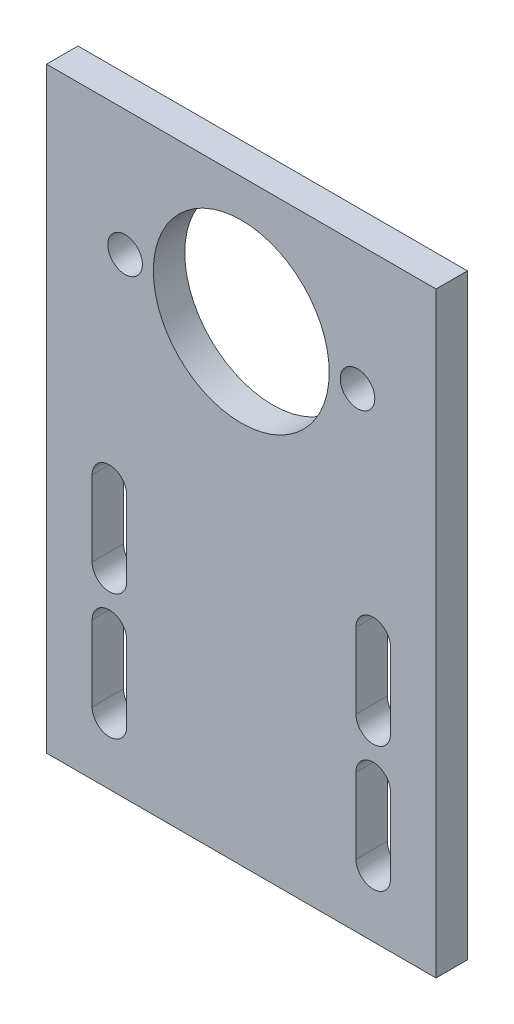
SolidWorks part; units mm, degrees
ref_plane "Front Plane" through (0, 0, 0) normal (0, 0, 1) x (1, 0, 0)
ref_plane "Top Plane" through (0, 0, 0) normal (0, 1, 0) x (1, 0, 0)
ref_plane "Right Plane" through (0, 0, 0) normal (1, 0, 0) x (0, 0, -1)
sketch "Sketch1" plane through (0, 0, 0) normal (0, 0, 1) x (1, 0, 0)
  line L0 (-4, 0) -> (-4, 100) construction
  line L1 (-35, -15) -> (27, -15) construction
  line L2 (-35, -15) -> (-35, 100)
  line L3 (-35, 100) -> (27, 100)
  line L4 (27, -15) -> (27, 100)
  line L5 (-35, -15) -> (27, 100) construction
  line L6 (-35, 100) -> (27, -15) construction
  line L7 (-22.5, 40) -> (14.5, 40) construction
  line L8 (-4, 0) -> (-4, -15) construction
  line L9 (-25, -5) -> (17, -5) construction
  line L10 (-35, -15) -> (-35, -35)
  line L11 (-25, -5) -> (-25, 7) construction
  line L12 (-35, -35) -> (27, -35)
  line L13 (27, -35) -> (27, -15)
  line L14 (-27.75, -5) -> (-27.75, 7)
  line L15 (-22.25, -5) -> (-22.25, 7)
  line L16 (17, -5) -> (17, 7) construction
  line L17 (19.75, -5) -> (19.75, 7)
  line L18 (14.25, -5) -> (14.25, 7)
  line L19 (-25, -25) -> (-25, -13) construction
  line L20 (-27.75, -25) -> (-27.75, -13)
  line L21 (-22.25, -25) -> (-22.25, -13)
  line L22 (17, -25) -> (17, -13) construction
  line L23 (19.75, -25) -> (19.75, -13)
  line L24 (14.25, -25) -> (14.25, -13)
  line L25 (-35, 60) -> (27, 60)
  circle A0 centre (-22.5, 40) radius 2.75
  circle A1 centre (14.5, 40) radius 2.75
  circle A2 centre (-4, 40) radius 5
  circle A3 centre (-25, -5) radius 2.75 construction
  circle A4 centre (17, -5) radius 2.75 construction
  circle A5 centre (17, -25) radius 2.75 construction
  circle A6 centre (-25, -25) radius 2.75 construction
  circle A7 centre (-4, 40) radius 14
  arc A8 (-27.75, -5) -> (-22.25, -5) centre (-25, -5) ccw
  arc A9 (-22.25, 7) -> (-27.75, 7) centre (-25, 7) ccw
  arc A10 (19.75, -5) -> (14.25, -5) centre (17, -5) cw
  arc A11 (14.25, 7) -> (19.75, 7) centre (17, 7) cw
  circle A12 centre (17, -5) radius 2.75 construction
  arc A13 (-27.75, -25) -> (-22.25, -25) centre (-25, -25) ccw
  arc A14 (-22.25, -13) -> (-27.75, -13) centre (-25, -13) ccw
  arc A15 (19.75, -25) -> (14.25, -25) centre (17, -25) cw
  arc A16 (14.25, -13) -> (19.75, -13) centre (17, -13) cw
  circle A17 centre (17, -25) radius 2.75 construction
  point P0 (-4, 42.5)
  point P5 (-25, 1)
  point P10 (-4, 40)
  point P18 (-4, -5)
  point P34 (17, 1)
  point P41 (-25, -19)
  point P48 (17, -19)
  dimension "D4" = 5.5
  dimension "D5" = 10
  dimension "D6" = 5.5
  dimension "D11" = 28
  dimension "D14" = 2.75
  dimension "D15" = 2.75
  dimension "D1" = 62
  dimension "D2" = 115
  dimension "D3" = 37
  dimension "D7" = 10
  dimension "D8" = 60
  dimension "D9" = 10
  dimension "D10" = 20
  dimension "D12" = 10
  dimension "D13" = 12
  dimension "D16" = 12
  dimension "D17" = 40
extrude "Boss-Extrude1" add sketch "Sketch1" along normal blind 5 contours L25 L2 L10 L12 L13 L4 A14 L21 A13 L20 A9 L15 A8 L14 A7 A1 A0 L18 A11 L17 A10 L24 A16 L23 A15 region at (-4, 10.3387, 0)
